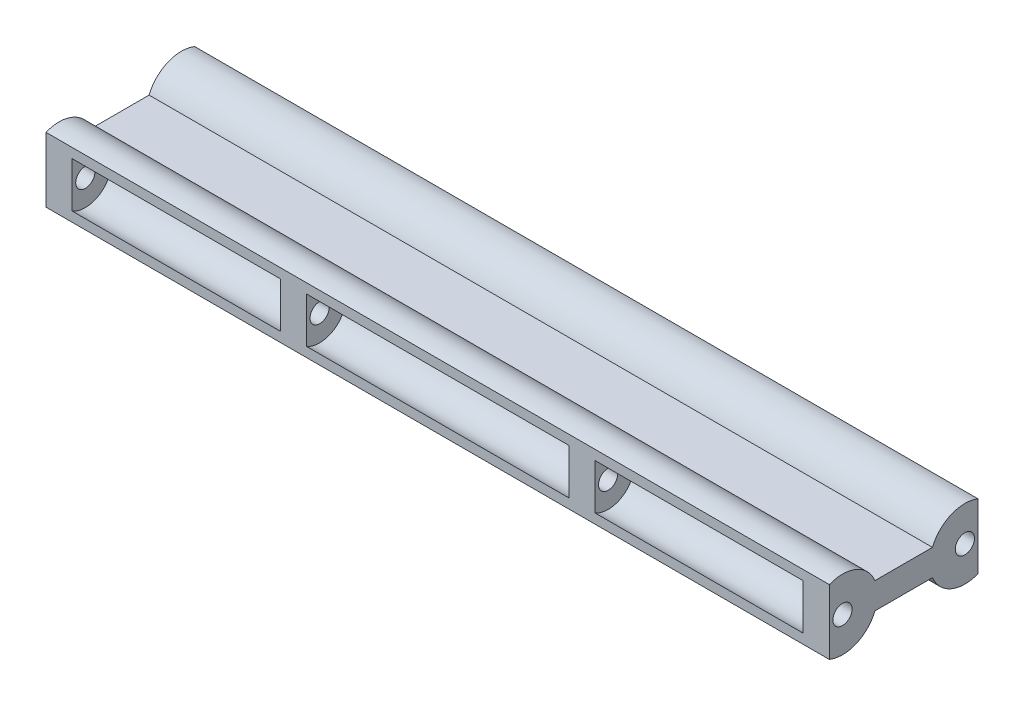
SolidWorks part; units mm, degrees
ref_plane "前视基准面" through (0, 0, 0) normal (0, 0, 1) x (1, 0, 0)
ref_plane "上视基准面" through (0, 0, 0) normal (0, 1, 0) x (1, 0, 0)
ref_plane "右视基准面" through (0, 0, 0) normal (1, 0, 0) x (0, 0, -1)
sketch "草图1" plane through (0, 0, 0) normal (1, 0, 0) x (0, 0, -1)
  line L0 (-7, 0) -> (7, 0) construction
  line L1 (8.5, -2.5981) -> (8.5, 2.5981) construction
  line L2 (-3.2919, 1.5) -> (3.2919, 1.5)
  line L3 (-3.2919, 1.5) -> (-3.2919, -1.5) construction
  line L4 (-3.2919, -1.5) -> (3.2919, -1.5)
  line L5 (3.2919, 1.5) -> (3.2919, -1.5) construction
  line L6 (-3.2919, 1.5) -> (3.2919, -1.5) construction
  line L7 (-3.2919, -1.5) -> (3.2919, 1.5) construction
  line L8 (-4.042, 0.5) -> (4.042, 0.5)
  line L9 (-4.042, 0.5) -> (-4.042, 0) construction
  line L10 (-4.042, -0.5) -> (4.042, -0.5)
  line L11 (4.042, 0) -> (4.042, -0.5) construction
  line L12 (-4.042, 0.5) -> (4.042, -0.5) construction
  line L13 (-4.042, -0.5) -> (4.042, 0.5) construction
  line L14 (-8.5, -3.7081) -> (8.5, -3.7081) construction
  line L15 (-8.5, -3.7081) -> (-8.5, -2.5981)
  line L16 (-8.5, 3.7081) -> (8.5, 3.7081) construction
  line L17 (8.5, -3.7081) -> (8.5, -2.5981)
  line L18 (-8.5, -3.7081) -> (8.5, 3.7081) construction
  line L19 (-8.5, 3.7081) -> (8.5, -3.7081) construction
  line L20 (8.5, 2.5981) -> (8.5, 3.7081)
  line L21 (-8.5, -2.5981) -> (-8.5, 2.5981) construction
  line L22 (-8.5, 2.5981) -> (-8.5, 3.7081)
  line L23 (-4.042, 0) -> (-4.042, -0.5) construction
  line L24 (4.042, 0.5) -> (4.042, 0) construction
  arc A0 (-8.5, -2.5981) -> (-4.042, -0.5) centre (-7, 0) ccw
  arc A1 (-8.5, -3.7081) -> (-3.2919, -1.5) centre (-7, 0) ccw
  arc A2 (8.5, 2.5981) -> (4.042, 0.5) centre (7, 0) ccw
  arc A3 (8.5, 3.7081) -> (3.2919, 1.5) centre (7, 0) ccw
  arc A4 (-8.5, 3.7081) -> (-8.5, -3.7081) centre (-7, 0) ccw construction
  arc A5 (-8.5, 2.5981) -> (-8.5, -2.5981) centre (-7, 0) ccw construction
  arc A6 (8.5, -3.7081) -> (8.5, 3.7081) centre (7, 0) ccw construction
  arc A7 (8.5, -2.5981) -> (8.5, 2.5981) centre (7, 0) ccw construction
  arc A8 (-4.042, -0.5) -> (-4, 0) centre (-7, 0) ccw construction
  arc A9 (-4.042, 0.5) -> (-8.5, 2.5981) centre (-7, 0) ccw
  arc A10 (-4, 0) -> (-4.042, 0.5) centre (-7, 0) ccw construction
  arc A11 (-3, 0) -> (-3.0175, 0.3733) centre (-7, 0) ccw construction
  arc A12 (-3.2919, 1.5) -> (-8.5, 3.7081) centre (-7, 0) ccw
  arc A13 (-3.0175, -0.3733) -> (-3, 0) centre (-7, 0) ccw construction
  arc A14 (3.0175, 0.3733) -> (3, 0) centre (7, 0) ccw construction
  arc A15 (3.2919, -1.5) -> (8.5, -3.7081) centre (7, 0) ccw
  arc A16 (3, 0) -> (3.0175, -0.3733) centre (7, 0) ccw construction
  arc A17 (3.0175, -0.3733) -> (3.0314, -0.5) centre (7, 0) ccw construction
  arc A18 (-3.0175, 0.3733) -> (-3.0314, 0.5) centre (-7, 0) ccw construction
  arc A19 (-3.0314, -0.5) -> (-3.0175, -0.3733) centre (-7, 0) ccw construction
  arc A20 (4, 0) -> (4.042, -0.5) centre (7, 0) ccw construction
  arc A21 (4.042, -0.5) -> (8.5, -2.5981) centre (7, 0) ccw
  arc A22 (4.042, 0.5) -> (4, 0) centre (7, 0) ccw construction
  arc A23 (3.2616, 1.4229) -> (3.0314, 0.5) centre (7, 0) ccw construction
  arc A24 (3.0314, 0.5) -> (3.0175, 0.3733) centre (7, 0) ccw construction
  arc A25 (3.0314, -0.5) -> (3.2616, -1.4229) centre (7, 0) ccw construction
  arc A26 (-3.2616, -1.4229) -> (-3.0314, -0.5) centre (-7, 0) ccw construction
  arc A27 (-3.0314, 0.5) -> (-3.2616, 1.4229) centre (-7, 0) ccw construction
  arc A28 (-3.2919, -1.5) -> (-3.2616, -1.4229) centre (-7, 0) ccw construction
  arc A29 (-3.2616, 1.4229) -> (-3.2919, 1.5) centre (-7, 0) ccw construction
  arc A30 (3.2919, 1.5) -> (3.2616, 1.4229) centre (7, 0) ccw construction
  arc A31 (3.2616, -1.4229) -> (3.2919, -1.5) centre (7, 0) ccw construction
  point P4 (0, 0)
  point P9 (0, 0)
  point P14 (0, 0)
  point P19 (0, 0)
  dimension "D1" = 8
  dimension "D2" = 6
  dimension "D3" = 3
  dimension "D4" = 1
  dimension "D5" = 14
  dimension "D6" = 17
extrude "凸台-拉伸1" add sketch "草图1" along normal mid plane 30
sketch "草图2" plane through (0, 0, 0) normal (1, 0, 0) x (0, 0, -1)
  line L0 (-3.2919, -1.5) -> (3.2919, -1.5) construction
  line L1 (3.2919, 1.5) -> (-3.2919, 1.5) construction
  line L2 (-3.2919, -1.5) -> (3.2919, -1.5)
  line L3 (3.2919, 1.5) -> (-3.2919, 1.5)
  line L4 (-8.5, 3.7081) -> (-8.5, -3.7081)
  line L5 (8.5, -3.7081) -> (8.5, 3.7081)
  arc A0 (-8.5, -3.7081) -> (-3.2919, -1.5) centre (-7, 0) ccw construction
  arc A1 (3.2919, -1.5) -> (8.5, -3.7081) centre (7, 0) ccw construction
  arc A2 (8.5, 3.7081) -> (3.2919, 1.5) centre (7, 0) ccw construction
  arc A3 (-3.2919, 1.5) -> (-8.5, 3.7081) centre (-7, 0) ccw construction
  arc A4 (-8.5, -3.7081) -> (-3.2919, -1.5) centre (-7, 0) ccw
  arc A5 (3.2919, -1.5) -> (8.5, -3.7081) centre (7, 0) ccw
  arc A6 (8.5, 3.7081) -> (3.2919, 1.5) centre (7, 0) ccw
  arc A7 (-3.2919, 1.5) -> (-8.5, 3.7081) centre (-7, 0) ccw
extrude "凸台-拉伸2" add sketch "草图2" along normal blind 29.8 from surface starting at face at (15, 2.6375, 0)
extrude "凸台-拉伸3" add sketch "草图2<2>" against normal blind 29.8 from surface starting at face at (-15, -2.6375, 0)
sketch "草图2<2>" plane through (0, 0, 0) normal (1, 0, 0) x (0, 0, -1) same geometry as "草图2"
sketch "草图3" plane through (0, 0, 0) normal (1, 0, 0) x (0, 0, -1)
  line L0 (-4.042, 0.5) -> (-4.042, -0.5)
  line L1 (-8.5, -2.5981) -> (-8.5, 2.5981)
  line L2 (8.5, 2.5981) -> (8.5, -2.5981)
  line L3 (4.042, -0.5) -> (4.042, 0.5)
  arc A0 (-8.5, -2.5981) -> (-4.042, -0.5) centre (-7, 0) ccw construction
  arc A1 (-4.042, 0.5) -> (-8.5, 2.5981) centre (-7, 0) ccw construction
  arc A2 (4.042, -0.5) -> (8.5, -2.5981) centre (7, 0) ccw construction
  arc A3 (8.5, 2.5981) -> (4.042, 0.5) centre (7, 0) ccw construction
  arc A4 (-8.5, -2.5981) -> (-4.042, -0.5) centre (-7, 0) ccw
  arc A5 (-4.042, 0.5) -> (-8.5, 2.5981) centre (-7, 0) ccw
  arc A6 (4.042, -0.5) -> (8.5, -2.5981) centre (7, 0) ccw
  arc A7 (8.5, 2.5981) -> (4.042, 0.5) centre (7, 0) ccw
extrude "切除-拉伸1" cut sketch "草图3" along normal offset from surface (23.8 mm away) 3 from offset 18 up to face at (44.8, 0, 0)
extrude "切除-拉伸2" cut sketch "草图3<2>" against normal offset from surface (23.8 mm away) 3 from offset 18 up to face at (-44.8, 0, 0) offset against normal yes
sketch "草图3<2>" plane through (0, 0, 0) normal (1, 0, 0) x (0, 0, -1) same geometry as "草图3"
sketch "草图4" plane through (0, 0, 0) normal (1, 0, 0) x (0, 0, -1)
  circle A0 centre (-7, 0) radius 1.1
  circle A1 centre (7, 0) radius 1.1
  dimension "D1" = 2.2
extrude "切除-拉伸3" cut sketch "草图4" against normal through all both and the other way through all
